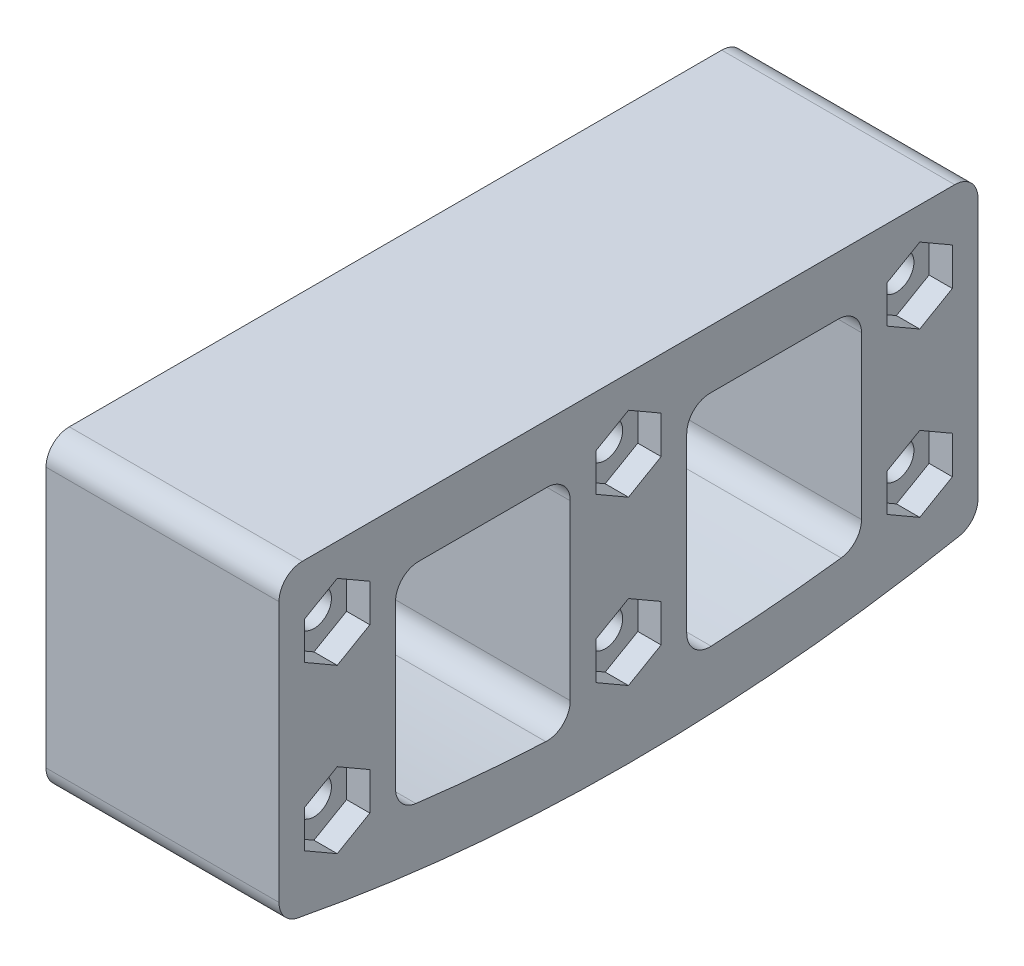
SolidWorks part; units mm, degrees
ref_plane "Front Plane" through (0, 0, 0) normal (0, 0, 1) x (1, 0, 0)
ref_plane "Top Plane" through (0, 0, 0) normal (0, 1, 0) x (1, 0, 0)
ref_plane "Right Plane" through (0, 0, 0) normal (1, 0, 0) x (0, 0, -1)
sketch "Sketch1" plane through (0, 0, 0) normal (1, 0, 0) x (0, 0, -1)
  line L0 (-28, 13.2162) -> (28, 13.2162)
  line L1 (30, 11.2162) -> (30, -11.1417)
  line L2 (30, -12.7838) -> (-30, -12.7838) construction
  line L3 (-30, -11.1417) -> (-30, 11.2162)
  line L4 (0, 97.3242) -> (0, -12.7838) construction
  line L6 (-25, 7.2162) -> (-25, -6.7838) construction
  line L8 (25, 7.2162) -> (25, -6.7838) construction
  line L10 (-25, 7.2162) -> (25, 7.2162) construction
  line L11 (25, -6.7838) -> (-25, -6.7838) construction
  line L14 (60.1589, 13.2162) -> (-78.8988, 13.2162) construction
  line L15 (-20, 6.2162) -> (-20, -7.6771)
  line L16 (-18, 8.2162) -> (-7, 8.2162)
  line L17 (-5, 6.2162) -> (-5, -8.643)
  line L18 (5, 6.2162) -> (5, -8.643)
  line L19 (7, 8.2162) -> (18, 8.2162)
  line L20 (20, 6.2162) -> (20, -7.6771)
  circle A0 centre (0, 7.2162) radius 1.5
  arc A1 (-28.3784, -13.1055) -> (28.3784, -13.1055) centre (0, 134.1856) ccw
  circle A2 centre (0, -6.7838) radius 1.5
  circle A3 centre (-25, 7.2162) radius 1.5
  circle A4 centre (-25, -6.7838) radius 1.5
  circle A5 centre (25, 7.2162) radius 1.5
  circle A6 centre (25, -6.7838) radius 1.5
  arc A7 (-18.2517, -9.6611) -> (-7.0979, -10.6406) centre (0, 134.1856) ccw
  arc A8 (7.0979, -10.6406) -> (18.2517, -9.6611) centre (0, 134.1856) ccw
  arc A9 (18.2517, -9.6611) -> (20, -7.6771) centre (18, -7.6771) ccw
  arc A10 (18, 8.2162) -> (20, 6.2162) centre (18, 6.2162) cw
  arc A11 (5, 6.2162) -> (7, 8.2162) centre (7, 6.2162) cw
  arc A12 (7.0979, -10.6406) -> (5, -8.643) centre (7, -8.643) cw
  arc A13 (-18.2517, -9.6611) -> (-20, -7.6771) centre (-18, -7.6771) cw
  arc A14 (-5, -8.643) -> (-7.0979, -10.6406) centre (-7, -8.643) cw
  arc A15 (-7, 8.2162) -> (-5, 6.2162) centre (-7, 6.2162) cw
  arc A16 (-20, 6.2162) -> (-18, 8.2162) centre (-18, 6.2162) cw
  arc A17 (28, 13.2162) -> (30, 11.2162) centre (28, 11.2162) cw
  arc A18 (30, -11.1417) -> (28.3784, -13.1055) centre (28, -11.1417) cw
  arc A19 (-28.3784, -13.1055) -> (-30, -11.1417) centre (-28, -11.1417) cw
  arc A20 (-28, 13.2162) -> (-30, 11.2162) centre (-28, 11.2162) ccw
  point P15 (0, 7.2162)
  point P62 (-30, 13.2162)
  dimension "D1" = 150
  dimension "D2" = 3
  dimension "D3" = 3
  dimension "D9" = 5
  dimension "D11" = 5
  dimension "D12" = 5
  dimension "D17" = 2
  dimension "D18" = 2
  dimension "D4" = 5
  dimension "D5" = 26
  dimension "D6" = 5
  dimension "D7" = 50
  dimension "D8" = 14
  dimension "D10" = 5
  dimension "D13" = 5
  dimension "D14" = 5
  dimension "D15" = 5
  dimension "D16" = 6
extrude "Boss-Extrude1" add sketch "Sketch1" along normal blind 20
sketch "Sketch2" plane through (0, 0, 0) normal (1, 0, 0) x (0, 0, -1)
  line L0 (-25, 13.2162) -> (-25, -12.7838) construction
  line L1 (-25, 3.983) -> (-22.2, 5.5996)
  line L2 (-22.2, 5.5996) -> (-22.2, 8.8327)
  line L3 (-22.2, 8.8327) -> (-25, 10.4493)
  line L4 (-25, 10.4493) -> (-27.8, 8.8327)
  line L5 (-27.8, 8.8327) -> (-27.8, 5.5996)
  line L6 (-27.8, 5.5996) -> (-25, 3.983)
  line L7 (-25, -10.017) -> (-22.2, -8.4004)
  line L8 (-22.2, -8.4004) -> (-22.2, -5.1673)
  line L9 (-22.2, -5.1673) -> (-25, -3.5507)
  line L10 (-25, -3.5507) -> (-27.8, -5.1673)
  line L11 (-27.8, -5.1673) -> (-27.8, -8.4004)
  line L12 (-27.8, -8.4004) -> (-25, -10.017)
  line L13 (0, 3.983) -> (2.8, 5.5996)
  line L14 (2.8, 5.5996) -> (2.8, 8.8327)
  line L15 (2.8, 8.8327) -> (0, 10.4493)
  line L16 (0, 10.4493) -> (-2.8, 8.8327)
  line L17 (-2.8, 8.8327) -> (-2.8, 5.5996)
  line L18 (-2.8, 5.5996) -> (0, 3.983)
  line L19 (0, -10.017) -> (2.8, -8.4004)
  line L20 (2.8, -8.4004) -> (2.8, -5.1673)
  line L21 (2.8, -5.1673) -> (0, -3.5507)
  line L22 (0, -3.5507) -> (-2.8, -5.1673)
  line L23 (-2.8, -5.1673) -> (-2.8, -8.4004)
  line L24 (-2.8, -8.4004) -> (0, -10.017)
  line L25 (25, 3.983) -> (27.8, 5.5996)
  line L26 (27.8, 5.5996) -> (27.8, 8.8327)
  line L27 (27.8, 8.8327) -> (25, 10.4493)
  line L28 (25, 10.4493) -> (22.2, 8.8327)
  line L29 (22.2, 8.8327) -> (22.2, 5.5996)
  line L30 (22.2, 5.5996) -> (25, 3.983)
  line L31 (25, -10.017) -> (27.8, -8.4004)
  line L32 (27.8, -8.4004) -> (27.8, -5.1673)
  line L33 (27.8, -5.1673) -> (25, -3.5507)
  line L34 (25, -3.5507) -> (22.2, -5.1673)
  line L35 (22.2, -5.1673) -> (22.2, -8.4004)
  line L36 (22.2, -8.4004) -> (25, -10.017)
  line L37 (0, 13.2162) -> (0, -12.7838) construction
  line L38 (25, 13.2162) -> (25, -12.7838) construction
  circle A0 centre (-25, 7.2162) radius 2.8 construction
  circle A1 centre (-25, -6.7838) radius 2.8 construction
  circle A2 centre (0, 7.2162) radius 2.8 construction
  circle A3 centre (0, -6.7838) radius 2.8 construction
  circle A4 centre (25, 7.2162) radius 2.8 construction
  circle A5 centre (25, -6.7838) radius 2.8 construction
  dimension "D1" = 5.6
  dimension "D2" = 5.6
  dimension "D3" = 5.6
  dimension "D4" = 5.6
  dimension "D5" = 5.6
  dimension "D6" = 5.6
extrude "Cut-Extrude1" cut sketch "Sketch2" along normal blind 2 from surface starting at face at (0, 7.2162, -26.5)
extrude "Cut-Extrude2" cut sketch "Sketch2<2>" against normal blind 2 from surface starting at face at (20, -6.7838, -26.5)
sketch "Sketch2<2>" plane through (0, 0, 0) normal (1, 0, 0) x (0, 0, -1) same geometry as "Sketch2"
